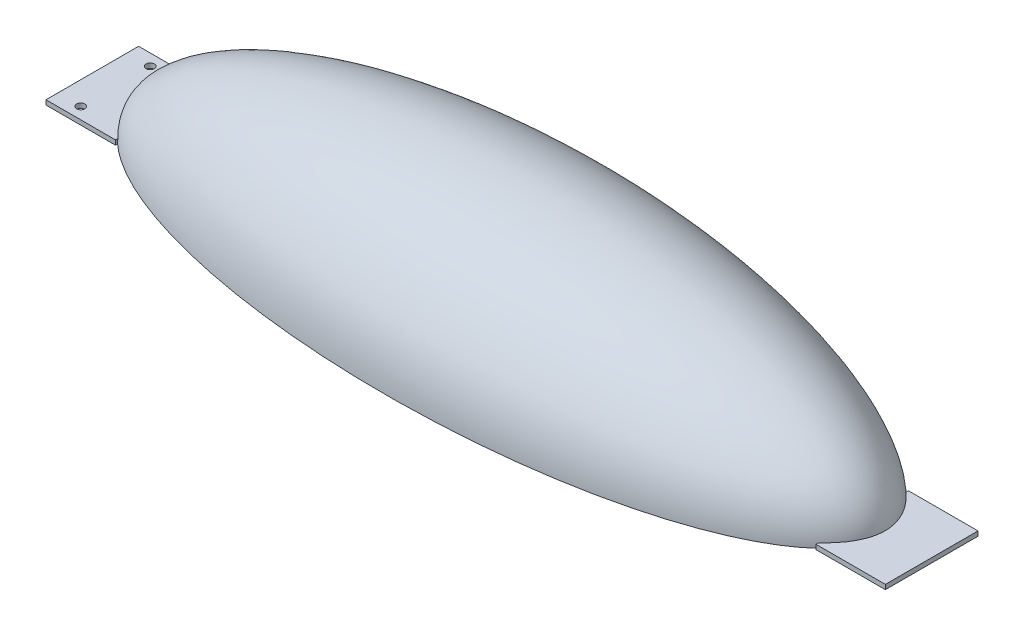
SolidWorks part; units mm, degrees
ref_plane "Front Plane" through (0, 0, 0) normal (0, 0, 1) x (1, 0, 0)
ref_plane "Top Plane" through (0, 0, 0) normal (0, 1, 0) x (1, 0, 0)
ref_plane "Right Plane" through (0, 0, 0) normal (1, 0, 0) x (0, 0, -1)
sketch "Sketch1" plane through (0, 0, 0) normal (0, 0, 1) x (1, 0, 0)
  line L0 (-322.5, 0) -> (0, 0)
  line L1 (10, 0) -> (-332.5, 0) construction
  ellipse E0 centre (-161.25, 0) end of major axis (0, 0) minor radius 55 (0, 0) -> (-322.5, 0) ccw
revolve "Revolve1" add sketch "Sketch1" angle 360 about L1
sketch "Sketch2" plane through (0, 0, 0) normal (0, 1, 0) x (1, 0, 0)
  line L0 (-372.5, 80) -> (50, 80)
  line L1 (50, 80) -> (50, -80)
  line L2 (50, -80) -> (-372.5, -80)
  line L3 (-372.5, -80) -> (-372.5, 80)
extrude "Cut-Extrude1" cut sketch "Sketch2" against normal blind 80
sketch "Sketch3" plane through (0, 0, 0) normal (0, 1, 0) x (1, 0, 0)
  line L0 (-342.5, 20) -> (-312.5, 20)
  line L1 (-312.5, 20) -> (-312.5, -20)
  line L2 (-312.5, -20) -> (-342.5, -20)
  line L3 (-342.5, -20) -> (-342.5, 20)
  line L4 (-10, 20) -> (20, 20)
  line L5 (20, 20) -> (20, -20)
  line L6 (20, -20) -> (-10, -20)
  line L7 (-10, -20) -> (-10, 20)
extrude "Boss-Extrude1" add sketch "Sketch3" along normal blind 2
sketch "Sketch4" plane through (0, 0, 0) normal (0, 1, 0) x (1, 0, 0)
  circle A0 centre (-332.5, -15) radius 1.8
  circle A1 centre (-332.5, 15) radius 1.8
extrude "Cut-Extrude2" cut sketch "Sketch4" along normal blind 3
